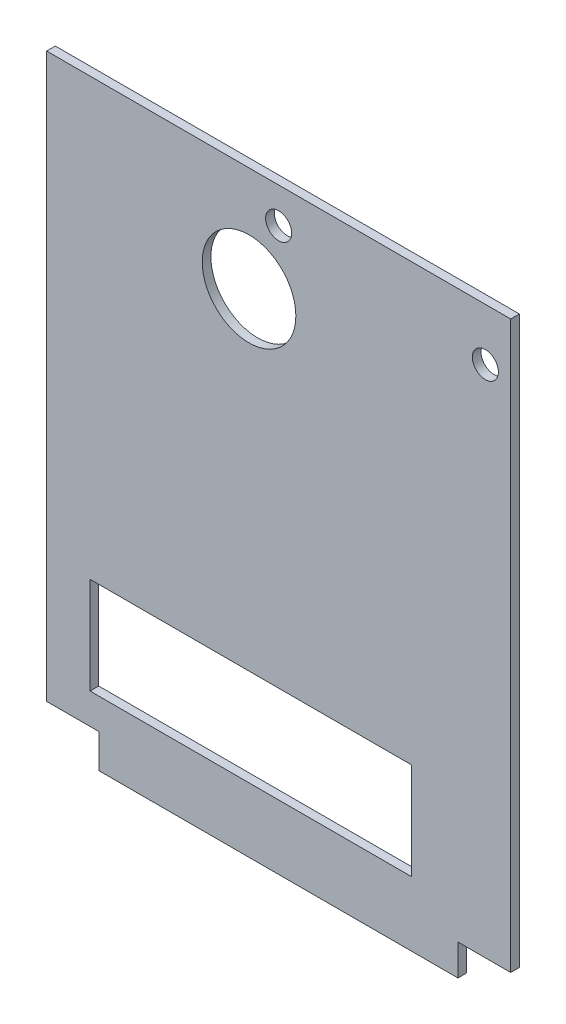
SolidWorks part; units mm, degrees
ref_plane "Front Plane" through (0, 0, 0) normal (0, 0, 1) x (1, 0, 0)
ref_plane "Top Plane" through (0, 0, 0) normal (0, 1, 0) x (1, 0, 0)
ref_plane "Right Plane" through (0, 0, 0) normal (1, 0, 0) x (0, 0, -1)
sketch "Sketch1" plane through (0, 0, 0) normal (0, 0, 1) x (1, 0, 0)
  line L1 (-42.814, 46.3633) -> (38.72, 46.3633)
  line L2 (-42.814, 46.3633) -> (-42.814, -58.5387)
  line L3 (-42.814, -58.5387) -> (38.72, -58.5387)
  line L4 (38.72, 46.3633) -> (38.72, -58.5387)
  dimension "D1" = 104.902
  dimension "D2" = 81.534
extrude "Boss-Extrude1" add sketch "Sketch1" along normal blind 1.524
sketch "Sketch2" plane through (0, 0, 1.524) normal (0, 0, 1) x (1, 0, 0)
  line L1 (-42.814, -58.5387) -> (-33.644, -58.5387)
  line L2 (-42.814, -58.5387) -> (-42.814, -52.5887)
  line L3 (-42.814, -52.5887) -> (-33.644, -52.5887)
  line L4 (-33.644, -58.5387) -> (-33.644, -52.5887)
  line L5 (38.72, -58.5387) -> (29.4539, -58.5387)
  line L6 (38.72, -58.5387) -> (38.72, -53.0667)
  line L7 (38.72, -53.0667) -> (29.4539, -53.0667)
  line L8 (29.4539, -58.5387) -> (29.4539, -53.0667)
  dimension "D1" = 9.17
  dimension "D2" = 5.95
extrude "Cut-Extrude1" cut sketch "Sketch2" against normal blind 1.524
sketch "Sketch4" plane through (0, 0, 1.524) normal (0, 0, 1) x (1, 0, 0)
  line L4 (-35.184, -47.1987) -> (21.316, -47.1987)
  line L5 (-35.184, -47.1987) -> (-35.184, -30.1987)
  line L6 (-35.184, -30.1987) -> (21.316, -30.1987)
  line L7 (21.316, -47.1987) -> (21.316, -30.1987)
  dimension "D3" = 17
  dimension "D4" = 56.5
extrude "Cut-Extrude2" cut sketch "Sketch4" against normal blind 1.524
sketch "Sketch6" plane through (0, 0, 1.524) normal (0, 0, 1) x (1, 0, 0)
  line L0 (38.72, 46.3633) -> (36.55, 46.3633)
  line L2 (38.72, 46.3633) -> (-42.814, 46.3633) construction
  circle A0 centre (-2.047, 40.1583) radius 2.285
  circle A1 centre (34.265, 37.1933) radius 2.285
  dimension "D2" = 4.57
extrude "Cut-Extrude3" cut sketch "Sketch6" against normal blind 1.524 contours A0 | A1 region at (-2.047, 40.1583, 1.524) region at (34.265, 37.1933, 1.524)
sketch "Sketch8" plane through (0, 0, 1.524) normal (0, 0, 1) x (1, 0, 0)
  circle A0 centre (-7.2531, 27.9572) radius 8.2241
extrude "Cut-Extrude4" cut sketch "Sketch8" against normal blind 2.54
